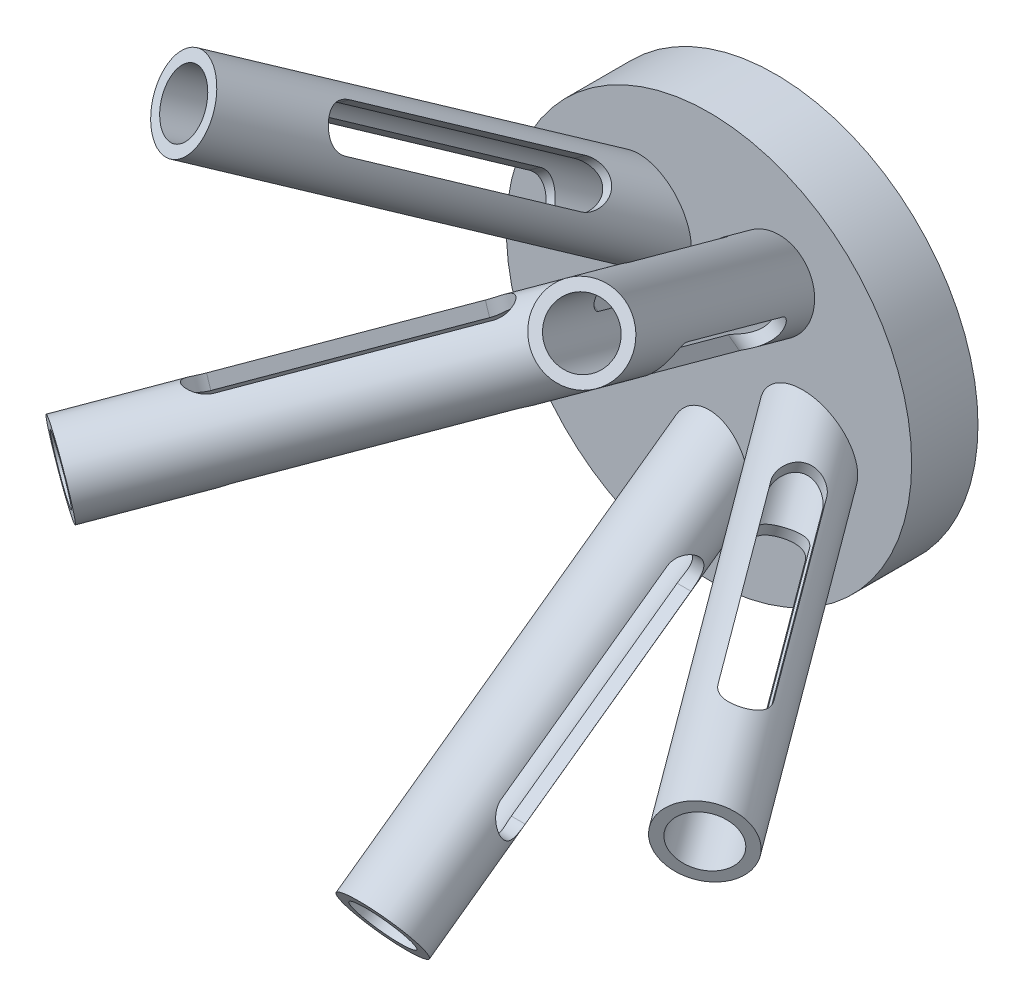
SolidWorks part; units mm, degrees
ref_plane "Front Plane" through (0, 0, 0) normal (0, 0, 1) x (1, 0, 0)
ref_plane "Top Plane" through (0, 0, 0) normal (0, 1, 0) x (1, 0, 0)
ref_plane "Right Plane" through (0, 0, 0) normal (1, 0, 0) x (0, 0, -1)
sketch "Sketch1" plane through (0, 0, 0) normal (0, 0, 1) x (1, 0, 0)
  circle A0 centre (0, 0) radius 55
  dimension "D1" = 110
extrude "Boss-Extrude1" add sketch "Sketch1" against normal mid plane 18 contours A0
sketch "Sketch2" plane through (0, 0, 0) normal (0, 0, 1) x (1, 0, 0)
  circle A0 centre (0, -22) radius 11
  dimension "D1" = 22
  dimension "D2" = 22
sketch "Sketch3" plane through (0, 0, 0) normal (1, 0, 0) x (0, 0, -1)
  line L0 (0, -22) -> (-97.537, -91.9037)
  line L1 (0, -11) -> (0, -33) construction
  dimension "D1" = 120
sweep "Sweep2" add path "Sketch3" circular profile diameter 22 parameters "D3"=22
sweep "Cut-Sweep1" cut path "Sketch3<2>" circular profile diameter 16 parameters "D3"=16
sketch "Sketch3<2>" plane through (0, 0, 0) normal (1, 0, 0) x (0, 0, -1) same geometry as "Sketch3"
sketch "Sketch534" plane through (0, 0, 0) normal (1, 0, 0) x (0, 0, -1)
  line L0 (-24.2373, -39.3706) -> (-74.0164, -75.0467)
  line L1 (0, -22) -> (-97.537, -91.9037) construction
  line L2 (-71.6218, -73.3305) -> (-26.6319, -41.0868) construction
  line L3 (-74.8777, -68.7876) -> (-29.8878, -36.5438)
  line L4 (-68.3659, -77.8735) -> (-23.376, -45.6298)
  arc A0 (-74.8777, -68.7876) -> (-68.3659, -77.8735) centre (-71.6218, -73.3305) ccw
  arc A1 (-23.376, -45.6298) -> (-29.8878, -36.5438) centre (-26.6319, -41.0868) ccw
  point P6 (-49.1269, -57.2087)
sketch "Sketch84" plane through (0, 0, 0) normal (1, 0, 0) x (0, 0, -1)
  line L0 (0, 0) -> (-200.8143, 0) construction
sketch "Sketch199" plane through (0, 0, 0) normal (1, 0, 0) x (0, 0, -1)
  line L0 (5.3176, -21.3084) -> (-9, -28.4502)
  line L1 (0, -22) -> (-97.537, -91.9037) construction
  line L2 (-9, -14.9169) -> (-9, -41.9835) construction
  dimension "D1" = 16
sweep "Cut-Sweep7" cut path "Sketch199" circular profile diameter 5 parameters "D3"=5
extrude "Cut-Extrude1" cut sketch "Sketch534" against normal blind 20 and the other way blind 20 contours L3 A1 L4 A0
pattern_circular "CirPattern1" count 5 over 360 about axis through (0, 0, 0) along (0, 0, 1) of "Sweep2", "Cut-Sweep1", "Cut-Sweep7", "Cut-Extrude1" reverse direction yes
sketch "Sketch535" plane through (0, 0, 0) normal (1, 0, 0) x (0, 0, -1)
  line L0 (9, -40) -> (4, -40)
  line L1 (9, -55) -> (9, 55) construction
  line L2 (4, -40) -> (4, -37)
  line L3 (4, -37) -> (-1, -37)
  line L4 (-1, -37) -> (-1, -47)
  line L5 (-1, -47) -> (4, -47)
  line L6 (4, -47) -> (4, -44)
  line L7 (4, -44) -> (9, -44)
  line L8 (9, -44) -> (9, -40)
  line L9 (-9, -55) -> (9, -55) construction
  dimension "D1" = 4
  dimension "D2" = 5
  dimension "D3" = 10
  dimension "D4" = 5
  dimension "D5" = 8
  dimension "D6" = 3
revolve "Cut-Revolve1" cut sketch "Sketch535" angle 360 about L0
